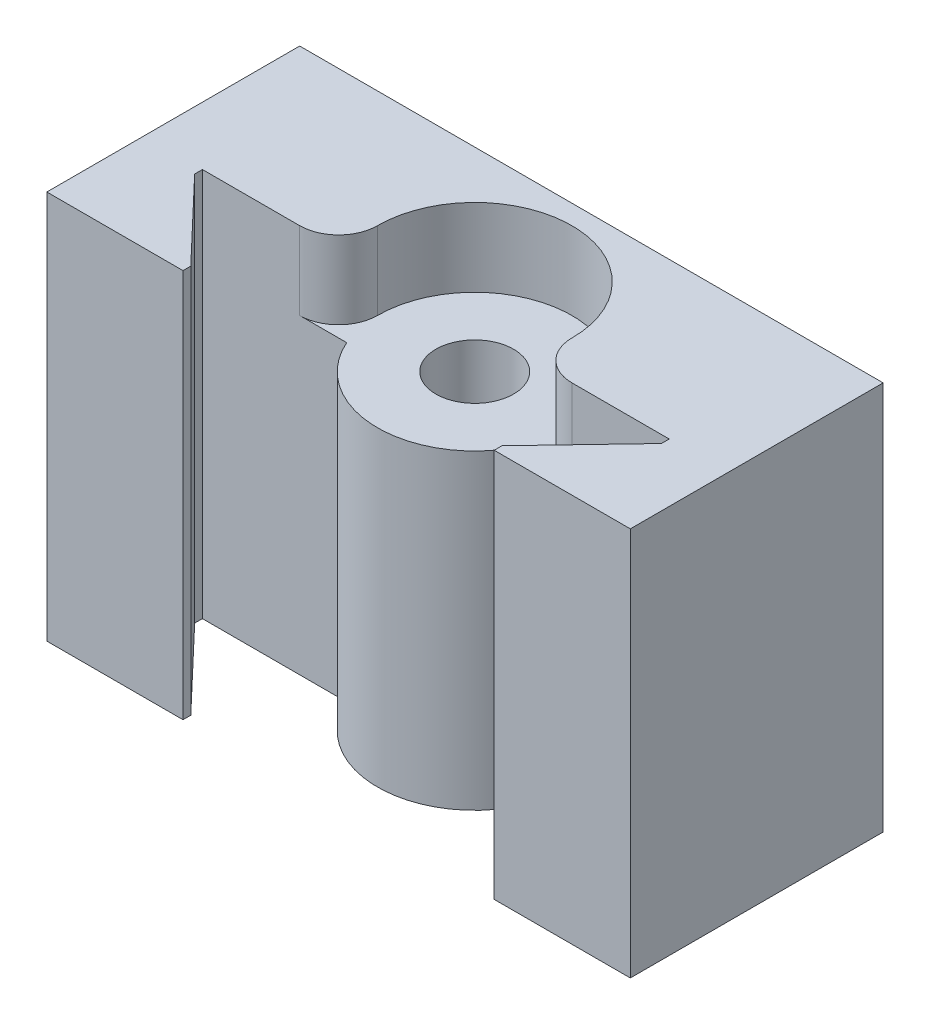
SolidWorks part; units mm, degrees
ref_plane "Front Plane" through (0, 0, 0) normal (0, 0, 1) x (1, 0, 0)
ref_plane "Top Plane" through (0, 0, 0) normal (0, 1, 0) x (1, 0, 0)
ref_plane "Right Plane" through (0, 0, 0) normal (1, 0, 0) x (0, 0, -1)
sketch "Sketch1" plane through (0, 0, 0) normal (0, 1, 0) x (1, 0, 0)
  line L0 (-8, 0) -> (8, 0)
  line L1 (8, 0) -> (8, 0.4)
  line L2 (0, 0) -> (0, 5)
  line L3 (-12, 5) -> (12, 5)
  line L4 (12, 5) -> (12, 4.6)
  line L5 (12, 4.6) -> (8, 0.4)
  line L6 (-8, 0) -> (-8, 0.4)
  line L7 (-12, 5) -> (-12, 4.6)
  line L8 (-12, 4.6) -> (-8, 0.4)
  line L9 (0, 5) -> (0, 7)
  line L10 (0, 7) -> (5, 7)
  line L11 (5, 7) -> (7, 7)
  line L12 (7, 7) -> (7, 5)
  line L13 (8, 0) -> (15, 0)
  line L14 (15, 0) -> (15, 13)
  line L15 (-8, 0) -> (-15, 0)
  line L16 (-15, 0) -> (-15, 13)
  line L17 (15, 13) -> (-15, 13)
  circle A0 centre (0, 7) radius 2
  circle A1 centre (0, 7) radius 5
  circle A2 centre (7, 7) radius 2
  circle A3 centre (-7, 7) radius 2
  dimension "D7" = 10
  dimension "D1" = 12
  dimension "D2" = 8
  dimension "D3" = 5
  dimension "D4" = 0.4
  dimension "D5" = 0.4
  dimension "D6" = 2
  dimension "D8" = 2
  dimension "D9" = 13
  dimension "D10" = 7
extrude "Boss-Extrude1" add sketch "Sketch1" along normal blind 20 contours L3 A3 A1 A2 L4 L5 L1 L13 L14 L17 L16 L15 L6 L8 L7 | A3 | L12 A2 L11 | L11 A2 L12 region at (-11.5, 0, -0.327) region at (-7, 0, -7) region at (6.1512, 0, -6.1512) region at (7.2829, 0, -7.2829)
extrude "Boss-Extrude2" add sketch "Sketch1<3>" along normal blind 16 contours L10 A1 L3 A0 | L3 A1 L10 A0 | L3 A1 L2 | L2 A1 L3 | A1 A3 L3 | A2 A1 L3 region at (-1.8166, 0, -3.7625) region at (1.8166, 0, -3.7625) region at (3.1891, 0, -5.9488) region at (-2.2913, 0, -5.1221) region at (-5.3088, 0, -5.4586) region at (5.3088, 0, -5.4586)
sketch "Sketch1<3>" plane through (0, 0, 0) normal (0, 1, 0) x (1, 0, 0) same geometry as "Sketch1"
